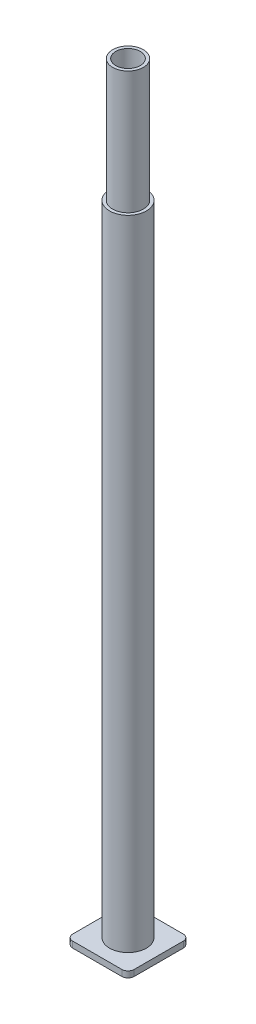
SolidWorks part; units mm, degrees
ref_plane "前视基准面" through (0, 0, 0) normal (0, 0, 1) x (1, 0, 0)
ref_plane "上视基准面" through (0, 0, 0) normal (0, 1, 0) x (1, 0, 0)
ref_plane "右视基准面" through (0, 0, 0) normal (1, 0, 0) x (0, 0, -1)
sketch "草图1" plane through (0, 0, 0) normal (0, 0, 1) x (1, 0, 0)
  line L0 (0, 0) -> (30, 0)
  line L3 (30, 0) -> (30, 1050)
  line L4 (25, 1250) -> (0, 1250)
  line L5 (0, 1250) -> (0, 0)
  line L6 (25, 1250) -> (25, 1050)
  line L7 (25, 1050) -> (30, 1050)
  dimension "D1" = 25
  dimension "D2" = 200
  dimension "D3" = 30
  dimension "D4" = 1250
revolve "旋转1" add sketch "草图1" angle 360 about L5
sketch "草图2" plane through (0, 0, 0) normal (0, -1, 0) x (1, 0, 0)
  line L1 (-50, 50) -> (50, 50)
  line L2 (-50, 50) -> (-50, -50)
  line L3 (-50, -50) -> (50, -50)
  line L4 (50, 50) -> (50, -50)
  line L5 (0, -50) -> (0, 50) construction
  line L6 (-50, 0) -> (50, 0) construction
  point P0 (0, 0)
  dimension "D1" = 100
  dimension "D2" = 100
extrude "凸台-拉伸1" add sketch "草图2" against normal blind 10
fillet "圆角1" radius 10 4 edges at (50, 5, -50) (-50, 5, -50) (-50, 5, 50) (50, 5, 50)
shell "抽壳1" thickness 5 removed face at (-25, 1250, 0)
